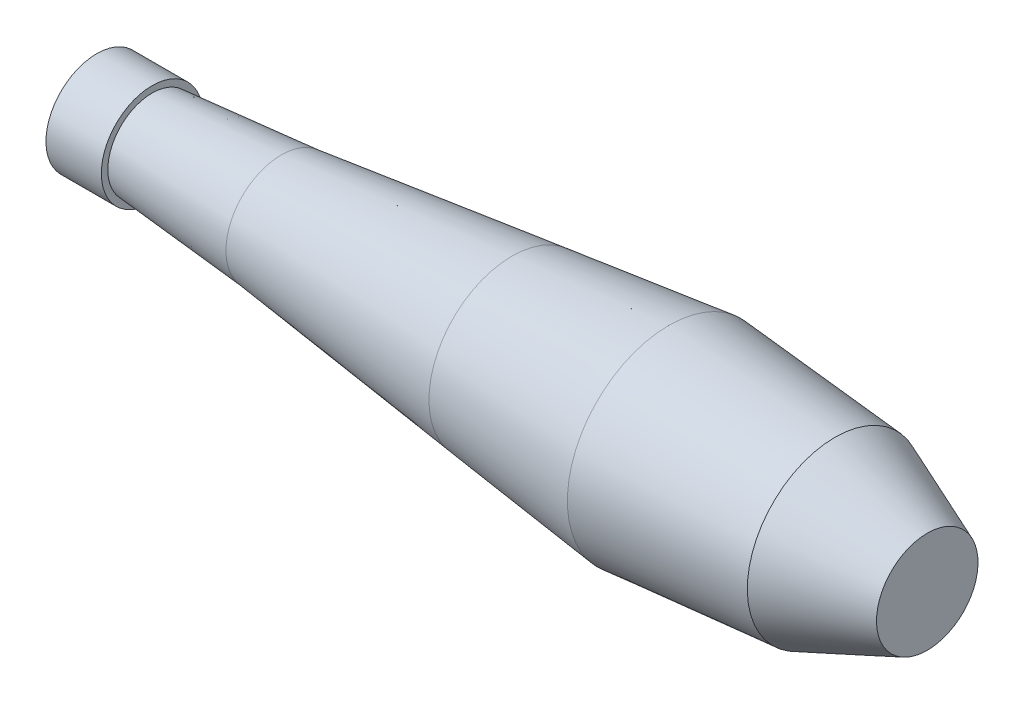
SolidWorks part; units mm, degrees
material "Oak"
ref_plane "Front Plane" through (0, 0, 0) normal (0, 0, 1) x (1, 0, 0)
ref_plane "Top Plane" through (0, 0, 0) normal (0, 1, 0) x (1, 0, 0)
ref_plane "Right Plane" through (0, 0, 0) normal (1, 0, 0) x (0, 0, -1)
sketch "Sketch1" plane through (0, 0, 0) normal (0, 0, 1) x (1, 0, 0)
  line L0 (0, 0) -> (90, 0) construction
  line L1 (0, 0) -> (0, 5.5)
  line L2 (0, 5.5) -> (6, 5.5)
  line L3 (6, 5.5) -> (6, 4.8)
  line L4 (6, 4.8) -> (20, 6)
  line L5 (20, 6) -> (45, 9)
  line L6 (45, 9) -> (62, 11)
  line L7 (62, 11) -> (80, 9.5)
  line L8 (80, 9.5) -> (90, 5.5)
  line L9 (90, 5.5) -> (90, 0)
  line L10 (90, 0) -> (0, 0)
revolve "Revolve1" add sketch "Sketch1" angle 360 about L0
